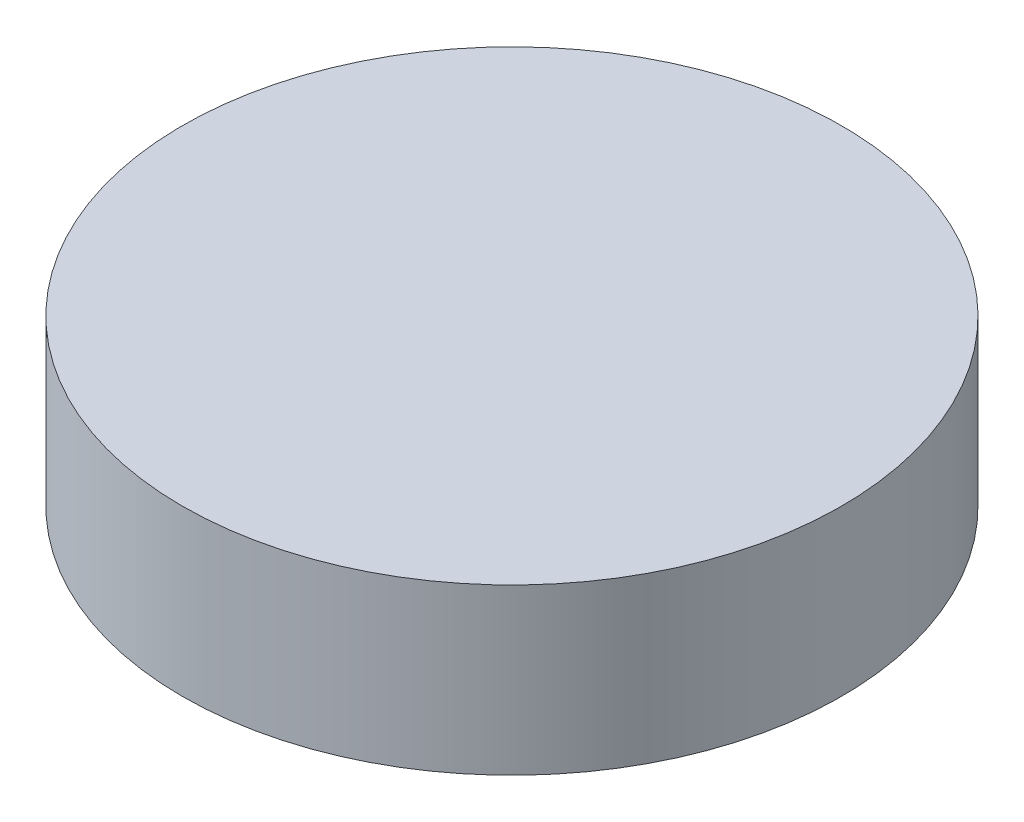
SolidWorks part; units mm, degrees
ref_plane "Piano frontale" through (0, 0, 0) normal (0, 0, 1) x (1, 0, 0)
ref_plane "Piano superiore" through (0, 0, 0) normal (0, 1, 0) x (1, 0, 0)
ref_plane "Piano destro" through (0, 0, 0) normal (1, 0, 0) x (0, 0, -1)
sketch "Schizzo1" plane through (0, 0, 0) normal (0, 1, 0) x (1, 0, 0)
  circle A0 centre (0, 0) radius 1
  dimension "D1" = 2
extrude "Estrusione-Estrusione1" add sketch "Schizzo1" along normal blind 0.5
ref_axis "Assi1" through (0, -7.1735, 0) along (0, 1, 0)
